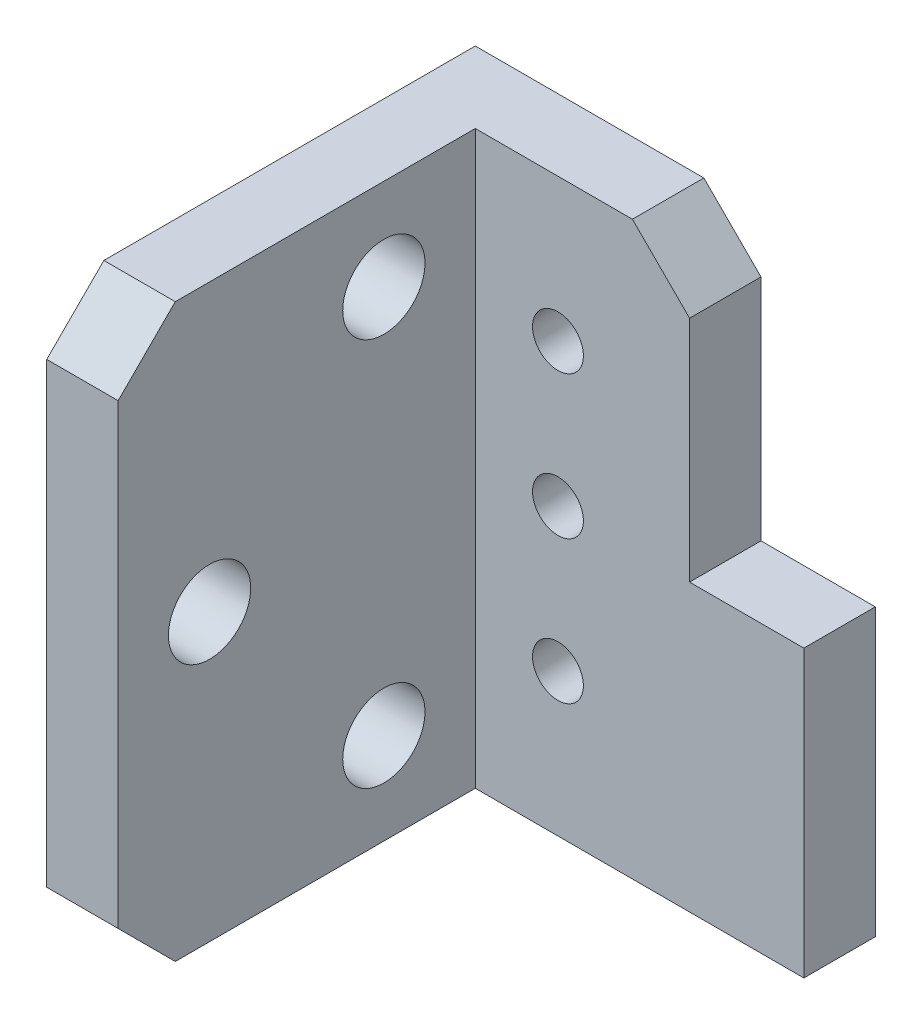
SolidWorks part; units mm, degrees
material "6061-T6 (SS)"
ref_plane "Front" through (0, 0, 0) normal (0, 0, 1) x (1, 0, 0)
ref_plane "Top" through (0, 0, 0) normal (0, 1, 0) x (1, 0, 0)
ref_plane "Right" through (0, 0, 0) normal (1, 0, 0) x (0, 0, -1)
ref_axis "side-side" through (80.9, 0, 0) along (-1, 0, 0)
ref_axis "up-down" through (0, 50, 0) along (0, -1, 0)
ref_axis "front-back" through (0, 0, -80.9) along (0, 0, 1)
sketch "Sketch1" plane through (0, 0, 0) normal (0, 1, 0) x (1, 0, 0)
  line L1 (0, 0) -> (12.7, 0)
  line L2 (0, 0) -> (0, -19.05)
  line L3 (0, -19.05) -> (3.175, -19.05)
  line L4 (12.7, 0) -> (12.7, -3.175)
  line L7 (12.7, -3.175) -> (3.175, -3.175)
  line L8 (3.175, -19.05) -> (3.175, -3.175)
  point P8 (7.9375, -3.175)
  dimension "D1" = 3.175
  dimension "D2" = 12.7
  dimension "D3" = 19.05
extrude "Boss-Extrude1" add sketch "Sketch1" along normal blind 25.4
sketch "Sketch2" plane through (0, 0, 0) normal (-1, 0, 0) x (0, 0, 1)
  line L0 (3.175, 25.4) -> (3.175, 0) construction
  line L1 (19.05, 25.4) -> (19.05, 0) construction
  line L2 (0, 25.4) -> (19.05, 25.4) construction
  line L3 (0, 0) -> (19.05, 0) construction
  line L4 (7.239, 21.336) -> (7.239, 4.064) construction
  line L5 (7.239, 12.7) -> (14.986, 12.7) construction
  circle A0 centre (14.986, 12.7) radius 1.8034
  circle A1 centre (7.239, 21.336) radius 1.8034
  circle A2 centre (7.239, 4.064) radius 1.8034
  dimension "D4" = 4.064
  dimension "D5" = 3.6068
  dimension "D1" = 4.064
  dimension "D2" = 4.064
  dimension "D3" = 4.064
hole_wizard "#6 Clearance Hole1" positions "Sketch3" profile "Sketch4" hole size "#6" standard "ANSI Inch" end condition through all
sketch "Sketch3" plane through (0, 0, 0) normal (-1, 0, 0) x (0, 0, 1)
  point P0 (7.239, 4.064)
  point P2 (7.239, 21.336)
  point P5 (14.986, 12.7)
sketch "Sketch4" plane through (0, 4.064, 7.239) normal (0, 1, 0) x (0, 0, 1)
  line L0 (0, 0) -> (0, 12.7)
  line L1 (0, 12.7) -> (1.8288, 12.7)
  line L2 (1.8288, 12.7) -> (1.8288, 0)
  line L5 (1.8288, 0) -> (0, 0)
  line L11 (0, -6.35) -> (0, 107.95) construction
  dimension "Thru Hole Dia." = 3.6576
  dimension "Thru Hole Depth" = 12.7
chamfer "Chamfer1" distance 2.54 angle 45 4 edges at (12.7, 0, 1.5875) (12.7, 25.4, 1.5875) (1.5875, 0, 19.05) (1.5875, 25.4, 19.05)
sketch "Sketch5" plane through (0, 0, 0) normal (0, 0, -1) x (-1, 0, 0)
  line L0 (-6.85, 25.4) -> (-6.85, 7.7906) construction
  line L1 (-10.16, 25.4) -> (0, 25.4) construction
  dimension "D1" = 1.4
hole_wizard "#4-40 Tapped Hole1" positions "Sketch6" profile "Sketch7" tap size "#4-40" standard "ANSI Inch" end condition through all
sketch "Sketch6" plane through (0, 0, 0) normal (0, 0, -1) x (-1, 0, 0)
  line L0 (-6.85, 25.4) -> (-6.85, 7.7906) construction
  line L1 (-12.7, 12.7) -> (-19.0301, 12.7) construction
  line L2 (-12.7, 22.86) -> (-12.7, 2.54) construction
  point P0 (-6.85, 6.35)
  point P4 (-6.85, 12.7)
  point P8 (-6.85, 19.05)
  dimension "D1" = 6.35
  dimension "D2" = 6.35
sketch "Sketch7" plane through (6.85, 6.35, 0) normal (1, 0, 0) x (0, 1, 0)
  line L0 (0, 0) -> (0, 19.05)
  line L1 (0, 19.05) -> (1.1303, 19.05)
  line L2 (1.1303, 19.05) -> (1.1303, 0)
  line L5 (1.1303, 0) -> (0, 0)
  line L11 (0, -6.35) -> (0, 107.95) construction
  dimension "Thread Major Dia." = 2.2606
  dimension "Thru Tap Drill Depth" = 19.05
sketch "Sketch8" plane through (0, 0, 0) normal (0, 0, -1) x (-1, 0, 0)
  line L1 (-17.78, 12.7) -> (-10.16, 12.7)
  line L2 (-17.78, 12.7) -> (-17.78, 0)
  line L3 (-17.78, 0) -> (-10.16, 0)
  line L4 (-10.16, 12.7) -> (-10.16, 0)
  line L5 (-12.7, 22.86) -> (-12.7, 2.54) construction
  point P7 (0, 0)
  dimension "D1" = 12.7
  dimension "D2" = 5.08
extrude "Boss-Extrude2" add sketch "Sketch8" against normal up to surface (3.175 mm away) up to face at (5.7197, 6.35, 3.175)
